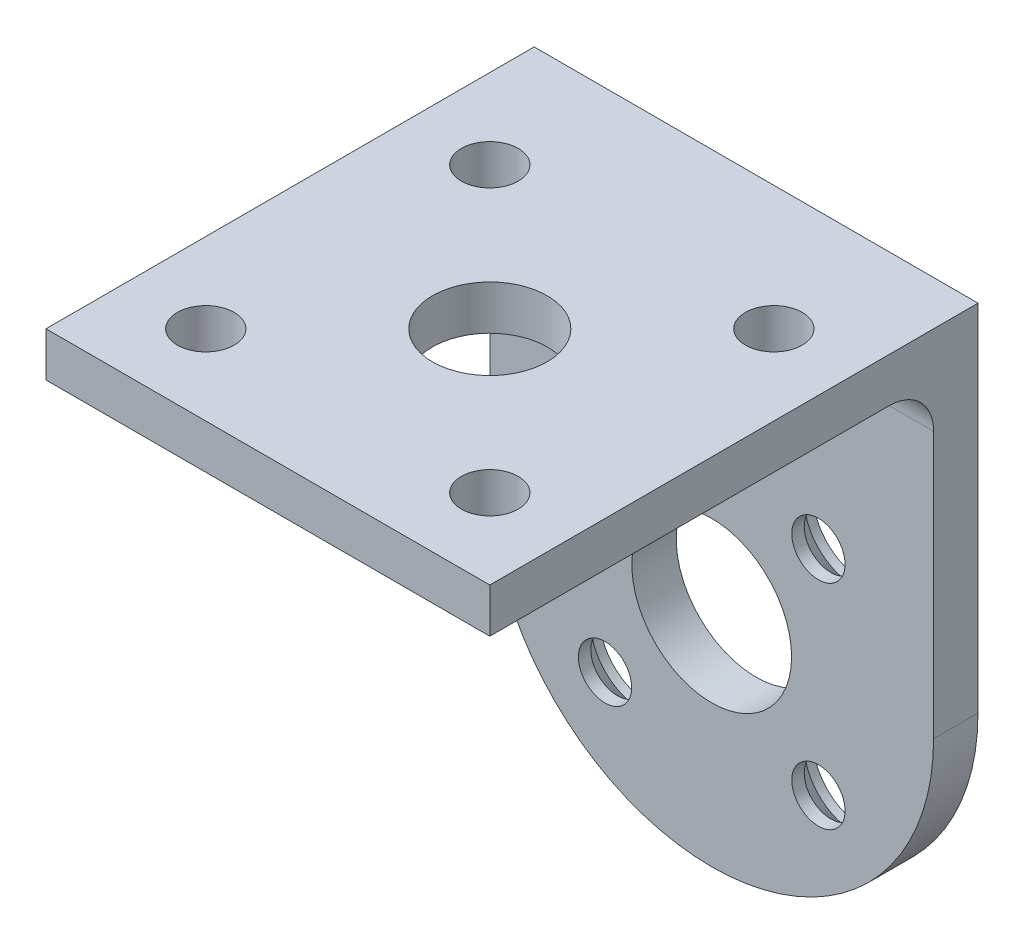
SolidWorks part; units mm, degrees
ref_plane "Front Plane" through (0, 0, 0) normal (0, 0, 1) x (1, 0, 0)
ref_plane "Top Plane" through (0, 0, 0) normal (0, 1, 0) x (1, 0, 0)
ref_plane "Right Plane" through (0, 0, 0) normal (1, 0, 0) x (0, 0, -1)
sketch "Sketch1" plane through (0, 0, 0) normal (0, 0, 1) x (1, 0, 0)
  line L0 (0, 0) -> (0, 20) construction
  line L6 (12.5, 0) -> (12.5, 20)
  line L7 (12.5, 20) -> (-12.5, 20)
  line L8 (-12.5, 0) -> (-12.5, 20)
  line L9 (0, 0) -> (12.5, 0) construction
  line L10 (0, 0) -> (6.0104, 6.0104) construction
  arc A0 (-12.5, 0) -> (12.5, 0) centre (0, 0) ccw
  circle A1 centre (0, 0) radius 4.5
  circle A2 centre (6.0104, 6.0104) radius 2.8
  circle A3 centre (6.0104, -6.0104) radius 2.8
  circle A4 centre (-6.0104, -6.0104) radius 2.8
  circle A5 centre (-6.0104, 6.0104) radius 2.8
  circle A6 centre (6.0104, 6.0104) radius 1.5
  circle A7 centre (6.0104, -6.0104) radius 1.5
  circle A8 centre (-6.0104, -6.0104) radius 1.5
  circle A9 centre (-6.0104, 6.0104) radius 1.5
  point P19 (0, 0)
  point P27 (0, 0)
  dimension "D1" = 25
  dimension "D3" = 9
  dimension "D4" = 5.6
  dimension "D8" = 3
  dimension "D10" = 5.6
  dimension "D2" = 20
  dimension "D5" = 8.5
  dimension "D6" = 45
  dimension "D7" = 4
  dimension "D9" = 4
extrude "Boss-Extrude1" add sketch "Sketch1" along normal blind 2.5 contours L8 A0 L6 L7 A5 A4 A3 A2 A1 region at (0, 6.3397, 0)
sketch "Sketch2" plane through (0, 0, 2.5) normal (0, 0, 1) x (1, 0, 0)
  line L0 (12.5, 0) -> (12.5, 20) construction
  line L3 (-12.5, 20) -> (12.5, 20)
  line L4 (-12.5, 20) -> (-12.5, 17.5)
  line L5 (-12.5, 17.5) -> (12.5, 17.5)
  line L6 (12.5, 20) -> (12.5, 17.5)
  dimension "D1" = 2.5
extrude "Boss-Extrude2" add sketch "Sketch2" along normal blind 25 contours L6 L3 L4 L5 region at (0, 18.75, 2.5)
fillet "Fillet1" radius 2.5 1 edges at (0, 17.5, 2.5)
sketch "Sketch4" plane through (0, 20, 0) normal (0, 1, 0) x (1, 0, 0)
  line L0 (12.5, -27.5) -> (-12.5, -27.5) construction
  line L2 (8, -23) -> (-8, -23)
  line L3 (8, -23) -> (8, -7)
  line L4 (8, -7) -> (-8, -7)
  line L5 (-8, -23) -> (-8, -7)
  line L6 (8, -23) -> (-8, -7) construction
  line L7 (8, -7) -> (-8, -23) construction
  circle A0 centre (0, -15) radius 3.2295
  circle A1 centre (-8, -7) radius 1.6
  circle A2 centre (8, -7) radius 1.6
  circle A3 centre (8, -23) radius 1.6
  circle A4 centre (-8, -23) radius 1.6
  dimension "D4" = 3.2
  dimension "D1" = 12.5
  dimension "D2" = 16
  dimension "D3" = 16
extrude "Cut-Extrude1" cut sketch "Sketch4" against normal blind 10 contours L5 A4 L2 | L2 A4 L5 | L2 A3 L3 | L3 A3 L2 | L3 A2 L4 | L4 A2 L3 | A0 | L4 A1 L5 | L5 A1 L4 region at (-8.2264, 20, 23.2264) region at (-7.3209, 20, 22.3209) region at (7.3209, 20, 22.3209) region at (8.2264, 20, 23.2264) region at (-8.2264, 20, 6.7736) region at (-7.3209, 20, 7.6791) region at (7.3209, 20, 7.6791) region at (8.2264, 20, 6.7736) region at (0, 20, 15)
sketch "Sketch3" plane through (0, 0, 0) normal (0, 0, -1) x (-1, 0, 0)
  circle A0 centre (-6.0104, 6.0104) radius 1.5
  circle A1 centre (6.0104, 6.0104) radius 1.5
  circle A2 centre (6.0104, -6.0104) radius 1.5
  circle A3 centre (-6.0104, -6.0104) radius 1.5
  point P12 (0, 0)
  circle M5 centre (6.0104, 6.0104) radius 2.8
  circle M6 centre (6.0104, -6.0104) radius 2.8
  circle M7 centre (-6.0104, -6.0104) radius 2.8
  circle M8 centre (-6.0104, 6.0104) radius 2.8
  dimension "D1" = 3
  dimension "D2" = 4
extrude "Boss-Extrude3" add sketch "Sketch3" along normal blind 0.5 from surface contours A0 M8 | A1 M5 | A2 M6 | A3 M7 region at (-3.2896, 6.0104, 0) region at (-3.2896, -6.0104, 0) region at (8.7312, -6.0104, 0) region at (8.7312, 6.0104, 0) starting at face at (0, 4.375, 2.5)
chamfer "Chamfer4" distance 1.5 angle 45 4 edges at (8.8104, 6.0104, 2) (-3.2104, -6.0104, 2) (8.8104, -6.0104, 2) (-3.2104, 6.0104, 2)
